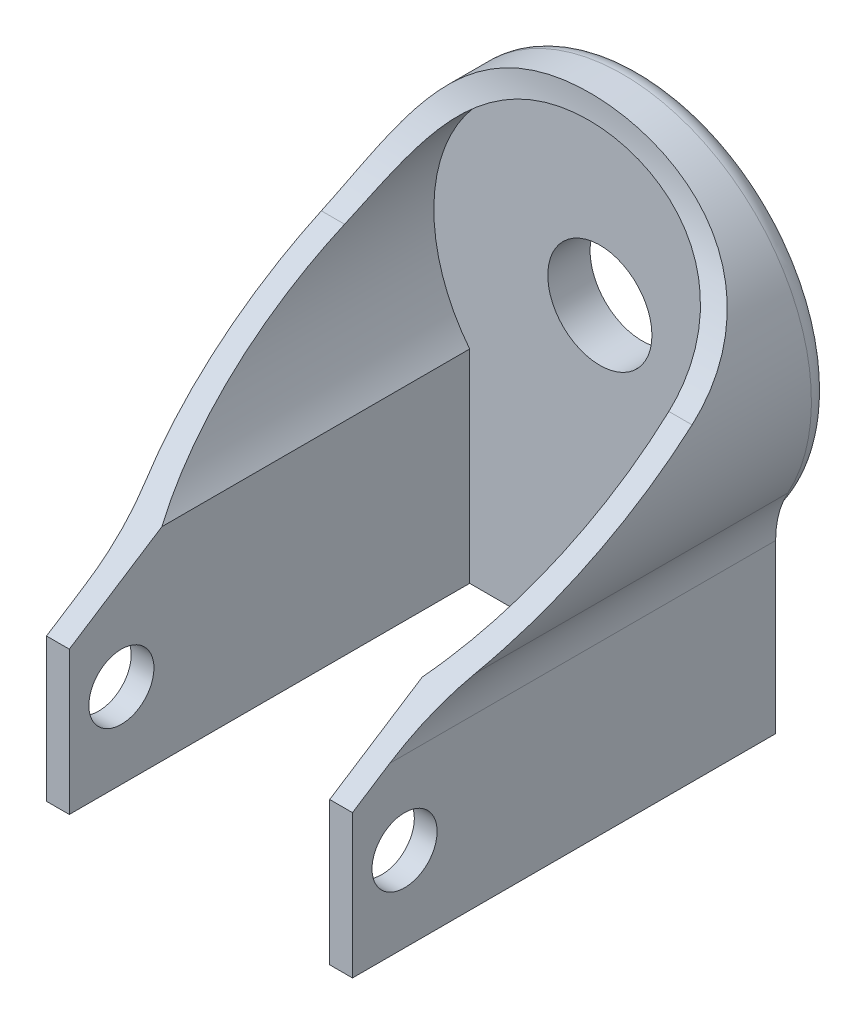
SolidWorks part; units mm, degrees
ref_plane "前视基准面" through (0, 0, 0) normal (0, 0, 1) x (1, 0, 0)
ref_plane "上视基准面" through (0, 0, 0) normal (0, 1, 0) x (1, 0, 0)
ref_plane "右视基准面" through (0, 0, 0) normal (1, 0, 0) x (0, 0, -1)
sketch "草图1" plane through (0, 0, 0) normal (0, 0, 1) x (1, 0, 0)
  line L0 (-23.5, -16.9926) -> (-23.5, -47)
  line L1 (-23.5, -47) -> (23.5, -47)
  line L2 (23.5, -47) -> (23.5, -16.9926)
  arc A0 (23.5, -16.9926) -> (-23.5, -16.9926) centre (0, 0) ccw
  point P6 (0, 0)
  point P8 (0, 0)
  point P9 (0, 0)
  point P10 (0, 0)
  dimension "D1" = 58
  dimension "D3" = 23.5
  dimension "D2" = 47
  dimension "D4" = 47
extrude "凸台-拉伸1" add sketch "草图1" along normal blind 65
shell "抽壳1" thickness 3.5
sketch "草图2" plane through (0, 0, 0) normal (1, 0, 0) x (0, 0, -1)
  line L0 (0, 29) -> (-65, 29) construction
  line L1 (-17.8087, 5.4793) -> (-65, -25)
  line L2 (-65, 29) -> (-65, -16.9926) construction
  arc A0 (-5, 29) -> (-17.8087, 5.4793) centre (-33, 29) cw
  point P3 (0, 0)
  point P9 (0, 0)
  point P10 (0, 0)
  point P11 (-65, 29)
  point P12 (0, 0)
  dimension "D1" = 28
  dimension "D2" = 60
  dimension "D3" = 54
  dimension "D4" = 0
extrude "切除-拉伸3" cut sketch "草图2" against normal through all and the other way through all flip side to cut
fillet "圆角1" radius 15 2 edges at (-23.5, -16.9926, 26.3011) (23.5, -16.9926, 26.3011)
sketch "草图3" plane through (0, 0, 65) normal (0, 0, 1) x (1, 0, 0)
  line L1 (-20, -43.5) -> (20, -43.5)
  line L2 (-20, -43.5) -> (-20, -47)
  line L3 (-20, -47) -> (20, -47)
  line L4 (20, -43.5) -> (20, -47)
  point P4 (0, 0)
  point P5 (0, 0)
  point P7 (0, 0)
  dimension "D1" = 40
  dimension "D2" = 3.5
extrude "切除-拉伸4" cut sketch "草图3" against normal blind 61.5
sketch "草图4" plane through (23.5, 0, 0) normal (1, 0, 0) x (0, 0, -1)
  line L0 (-65, -47) -> (0, -47) construction
  line L1 (0, -47) -> (0, -21.3014) construction
  circle A0 centre (-57, -34) radius 5
  dimension "D1" = 13
  dimension "D2" = 10
  dimension "D3" = 57
extrude "切除-拉伸5" cut sketch "草图4" against normal through all
sketch "草图5" plane through (0, 0, 0) normal (0, 0, -1) x (-1, 0, 0)
  circle A0 centre (0, 0) radius 29
  dimension "D1" = 58
extrude "凸台-拉伸2" add sketch "草图5" along normal blind 3
fillet "圆角2" radius 3 1 edges at (-29, 0, -3)
sketch "草图6" plane through (0, 0, 3.5) normal (0, 0, 1) x (1, 0, 0)
  circle A0 centre (0, 0) radius 8
  dimension "D1" = 16
extrude "切除-拉伸6" cut sketch "草图6" against normal through all
